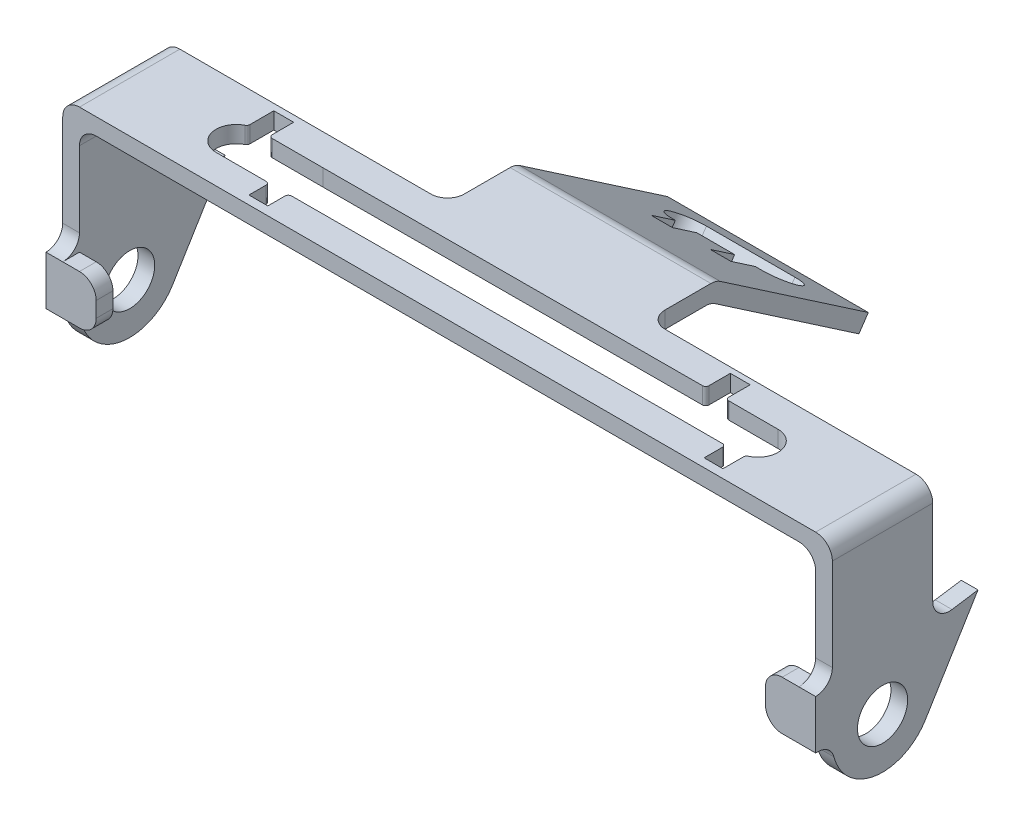
SolidWorks part; units mm, degrees
ref_plane "Front Plane" through (0, 0, 0) normal (0, 0, 1) x (1, 0, 0)
ref_plane "Top Plane" through (0, 0, 0) normal (0, 1, 0) x (1, 0, 0)
ref_plane "Right Plane" through (0, 0, 0) normal (1, 0, 0) x (0, 0, -1)
sketch "Sketch1" plane through (0, 0, 0) normal (0, 1, 0) x (1, 0, 0)
  line L1 (-110, 15) -> (110, 15)
  line L2 (-110, 15) -> (-110, -15)
  line L3 (-110, -15) -> (110, -15)
  line L4 (110, 15) -> (110, -15)
  line L5 (-110, 15) -> (110, -15) construction
  line L6 (-110, -15) -> (110, 15) construction
  point P0 (0, 0)
  dimension "D1" = 220
  dimension "D2" = 30
extrude "Boss-Extrude1" add sketch "Sketch1" along normal blind 5
sketch "Sketch2" plane through (-110, 0, 0) normal (-1, 0, 0) x (0, 0, 1)
  line L1 (-15, 5) -> (15, 5)
  line L2 (-15, 5) -> (-15, -65)
  line L3 (-15, -65) -> (15, -65)
  line L4 (15, 5) -> (15, -65)
  dimension "D1" = 30
  dimension "D2" = 70
extrude "Boss-Extrude2" add sketch "Sketch2" along normal blind 5
mirror "Mirror1" about plane through (0, 0, 0) normal (1, 0, 0) of "Boss-Extrude2"
sketch "Sketch4" plane through (-115, 0, 0) normal (-1, 0, 0) x (0, 0, 1)
  line L4 (-15, 5) -> (-15, -65)
  line L5 (-15, -65) -> (15, -65)
  line L6 (15, -65) -> (15, 5)
  line L7 (15, 5) -> (-15, 5)
  line L8 (-15, -47.1675) -> (-15, -65)
  line L9 (-15, -65) -> (15, -65)
  line L10 (15, -65) -> (15, -47.1675)
  arc A0 (-15, -47.1675) -> (15, -47.1675) centre (0, -47.1675) ccw
  dimension "D1" = 0
extrude "Cut-Extrude1" cut sketch "Sketch4" against normal blind 10
mirror "Mirror2" about plane through (0, 0, 0) normal (1, 0, 0) of "Cut-Extrude1"
sketch "Sketch5" plane through (115, 0, 0) normal (1, 0, 0) x (0, 0, -1)
  line L0 (28.5233, -29.2212) -> (15, -31.2888)
  line L1 (39.7357, -27.5068) -> (-6.1746, -34.5263) construction
  line L2 (15, 5) -> (15, -47.1675) construction
  line L3 (15, -31.2888) -> (-5.2015, -40.8909)
  line L4 (-5.2015, -40.8909) -> (-4.124, -59.0749)
  line L5 (-4.124, -59.0749) -> (0, -62.1675)
  line L6 (28.5233, -29.2212) -> (12.8043, -54.9809)
  arc A0 (-15, -47.1675) -> (15, -47.1675) centre (0, -47.1675) ccw construction
  arc A1 (0, -62.1675) -> (12.8043, -54.9809) centre (0, -47.1675) ccw
extrude "Boss-Extrude3" add sketch "Sketch5" against normal blind 5
mirror "Mirror3" about plane through (0, 0, 0) normal (1, 0, 0) of "Boss-Extrude3"
sketch "Sketch6" plane through (0, 0, 0) normal (1, 0, 0) x (0, 0, -1)
  line L0 (12.4709, 5) -> (35.2457, 5)
  line L1 (-15, 5) -> (15, 5) construction
  line L2 (35.2457, 5) -> (80.752, -26.0364)
  line L4 (12.4709, 0) -> (33.7029, 0)
  line L5 (33.7029, 0) -> (77.9348, -30.1671)
  line L6 (12.4709, 5) -> (12.4709, 0)
  line L7 (77.9348, -30.1671) -> (80.752, -26.0364)
  dimension "D1" = 5
extrude "Boss-Extrude4" add sketch "Sketch6" along normal mid plane 60
fillet "Fillet1" radius 5 10 edges at (30, 2.5, -15) (-30, 2.5, -15) (0, 0, -33.7029) (0, 5, -35.2457) (-112.5, -31.2888, -15) (-110, 0, 0) (-115, 5, 0) (115, 5, 0) (110, 0, 0) (112.5, -31.2888, -15)
sketch "Sketch7" plane through (-115, 0, 0) normal (-1, 0, 0) x (0, 0, 1)
  circle A0 centre (0, -47.1675) radius 7.5
  dimension "D1" = 15
extrude "Cut-Extrude2" cut sketch "Sketch7" against normal blind 253
sketch "Sketch8" plane through (0, 0, 15) normal (0, 0, 1) x (1, 0, 0)
  line L1 (-100, -32.5492) -> (-115, -32.5492)
  line L2 (-100, -32.5492) -> (-100, -47.1675)
  line L3 (-100, -47.1675) -> (-115, -47.1675)
  line L4 (-115, -32.5492) -> (-115, -47.1675)
  line L5 (100, -32.5492) -> (115, -32.5492)
  line L6 (100, -32.5492) -> (100, -47.1675)
  line L7 (100, -47.1675) -> (115, -47.1675)
  line L8 (115, -32.5492) -> (115, -47.1675)
extrude "Boss-Extrude5" add sketch "Sketch8" along normal blind 5
fillet "Fillet2" radius 5 8 edges at (100, -47.1675, 17.5) (100, -32.5492, 17.5) (112.5, -32.5492, 15) (112.5, -47.1675, 15) (-100, -47.1675, 17.5) (-100, -32.5492, 17.5) (-112.5, -47.1675, 15) (-112.5, -32.5492, 15)
sketch "Sketch9" plane through (0, 5, 0) normal (0, 1, 0) x (1, 0, 0)
  line L0 (57.753, 0) -> (77.753, 0) construction
  line L1 (57.753, 6) -> (77.753, 6)
  line L2 (57.753, -6) -> (77.753, -6)
  line L3 (-77.8469, -0.3196) -> (-57.8469, -0.3196) construction
  line L4 (-77.8469, 5.6804) -> (-57.8469, 5.6804)
  line L5 (-77.8469, -6.3196) -> (-57.8469, -6.3196)
  line L7 (-57.8469, 5.6804) -> (57.753, 6)
  line L8 (-57.8469, -6.3196) -> (57.753, -6)
  arc A0 (57.753, 6) -> (57.7198, 5.9999) centre (57.753, 0) ccw
  arc A1 (77.753, -6) -> (77.753, 6) centre (77.753, 0) ccw
  arc A2 (-77.8469, 5.6804) -> (-77.8469, -6.3196) centre (-77.8469, -0.3196) ccw
  arc A3 (-57.8469, -6.3196) -> (-57.8138, -6.3196) centre (-57.8469, -0.3196) ccw
  point P3 (67.753, 0)
  point P13 (-67.8469, -0.3196)
  dimension "D1" = 20
  dimension "D2" = 20
  dimension "D3" = 12
  dimension "D4" = 12
extrude "Cut-Extrude3" cut sketch "Sketch9" against normal blind 5 contours L4 A2 L5 L8 L2 A1 L1 L7 region at (-0.047, 5, 0.1598)
sketch "Sketch10" plane through (0, 5, 0) normal (0, 1, 0) x (1, 0, 0)
  line L0 (-53, 1.9143) -> (-83, 1.9143) construction
  line L1 (-80.005, 13.0821) -> (-74.0608, 13.0821)
  line L2 (-80.005, 13.0821) -> (-80.005, 1.9143)
  line L3 (-80.005, 1.9143) -> (-74.0608, 1.9143)
  line L4 (-74.0608, 13.0821) -> (-74.0608, 1.9143)
  line L5 (-80.005, 13.0821) -> (-74.0608, 1.9143) construction
  line L6 (-80.005, 1.9143) -> (-74.0608, 13.0821) construction
  line L8 (56.1604, 13.3526) -> (62.0887, 13.3526)
  line L9 (56.1604, 13.3526) -> (56.1604, 3.8456)
  line L10 (56.1604, 3.8456) -> (62.0887, 3.8456)
  line L11 (62.0887, 13.3526) -> (62.0887, 3.8456)
  line L12 (56.1604, 13.3526) -> (62.0887, 3.8456) construction
  line L13 (56.1604, 3.8456) -> (62.0887, 13.3526) construction
  line L14 (77.7869, 3.8456) -> (28.7869, 3.8456) construction
  point P0 (-77.0329, 7.4982)
  point P7 (59.1245, 8.5991)
extrude "Cut-Extrude4" cut sketch "Sketch10" against normal blind 5
sketch "Sketch11" plane through (0, 5, 0) normal (0, 1, 0) x (1, 0, 0)
  line L0 (53, -4.1019) -> (83, -4.1019) construction
  line L1 (79.7387, -12.4391) -> (74.1152, -12.4391)
  line L2 (79.7387, -12.4391) -> (79.7387, -4.1019)
  line L3 (79.7387, -4.1019) -> (74.1152, -4.1019)
  line L4 (74.1152, -12.4391) -> (74.1152, -4.1019)
  line L5 (79.7387, -12.4391) -> (74.1152, -4.1019) construction
  line L6 (79.7387, -4.1019) -> (74.1152, -12.4391) construction
  line L8 (-56.2766, -12.4391) -> (-61.9236, -12.4391)
  line L9 (-56.2766, -12.4391) -> (-56.2766, -3.335)
  line L10 (-56.2766, -3.335) -> (-61.9236, -3.335)
  line L11 (-61.9236, -12.4391) -> (-61.9236, -3.335)
  line L12 (-56.2766, -12.4391) -> (-61.9236, -3.335) construction
  line L13 (-56.2766, -3.335) -> (-61.9236, -12.4391) construction
  point P0 (76.927, -8.2705)
  point P7 (-59.1001, -7.887)
extrude "Cut-Extrude5" cut sketch "Sketch11" against normal blind 5
fillet "Fillet3" radius 1 8 edges at (-80.005, 2.5, -5.2788) (-61.9236, 2.5, 6.3196) (-74.0608, 2.5, -5.6804) (62.0887, 2.5, -6) (74.1152, 2.5, 6) (79.7387, 2.5, 5.6619) (56.1604, 2.5, -5.9956) (-56.2766, 2.5, 6.3153)
sketch "Sketch12" plane through (0, 19.8193, -13.5172) normal (0, 0.8261, -0.5635) x (1, 0, 0)
  line L0 (13.8392, 68.403) -> (-12.6156, 68.403) construction
  line L1 (13.8392, 62.403) -> (-12.6156, 62.403)
  line L2 (13.8392, 74.403) -> (-12.6156, 74.403)
  line L3 (130, 73.2655) -> (15, 73.2655) construction
  arc A0 (13.8392, 62.403) -> (13.8392, 74.403) centre (13.8392, 68.403) ccw
  arc A1 (-12.6156, 74.403) -> (-12.6156, 62.403) centre (-12.6156, 68.403) ccw
  point P2 (0.6118, 68.403)
  dimension "D1" = 12
  dimension "D2" = 4.8625
extrude "Cut-Extrude6" cut sketch "Sketch12" against normal blind 5
sketch "Sketch13" plane through (0, 19.8193, -13.5172) normal (0, 0.8261, -0.5635) x (1, 0, 0)
  line L0 (9.0941, 65.0642) -> (-20.9059, 65.0642) construction
  line L1 (11.8913, 53.5824) -> (5.7148, 53.5824)
  line L2 (11.8913, 53.5824) -> (11.8913, 65.0642)
  line L3 (11.8913, 65.0642) -> (5.7148, 65.0642)
  line L4 (5.7148, 53.5824) -> (5.7148, 65.0642)
  line L5 (11.8913, 53.5824) -> (5.7148, 65.0642) construction
  line L6 (11.8913, 65.0642) -> (5.7148, 53.5824) construction
  line L8 (-5.586, 64.4145) -> (-11.9998, 64.4145)
  line L9 (-5.586, 64.4145) -> (-5.586, 53.5824)
  line L10 (-5.586, 53.5824) -> (-11.9998, 53.5824)
  line L11 (-11.9998, 64.4145) -> (-11.9998, 53.5824)
  line L12 (-5.586, 64.4145) -> (-11.9998, 53.5824) construction
  line L13 (-5.586, 53.5824) -> (-11.9998, 64.4145) construction
  point P0 (8.8031, 59.3233)
  point P7 (-8.7929, 58.9985)
extrude "Cut-Extrude7" cut sketch "Sketch13" against normal blind 5
